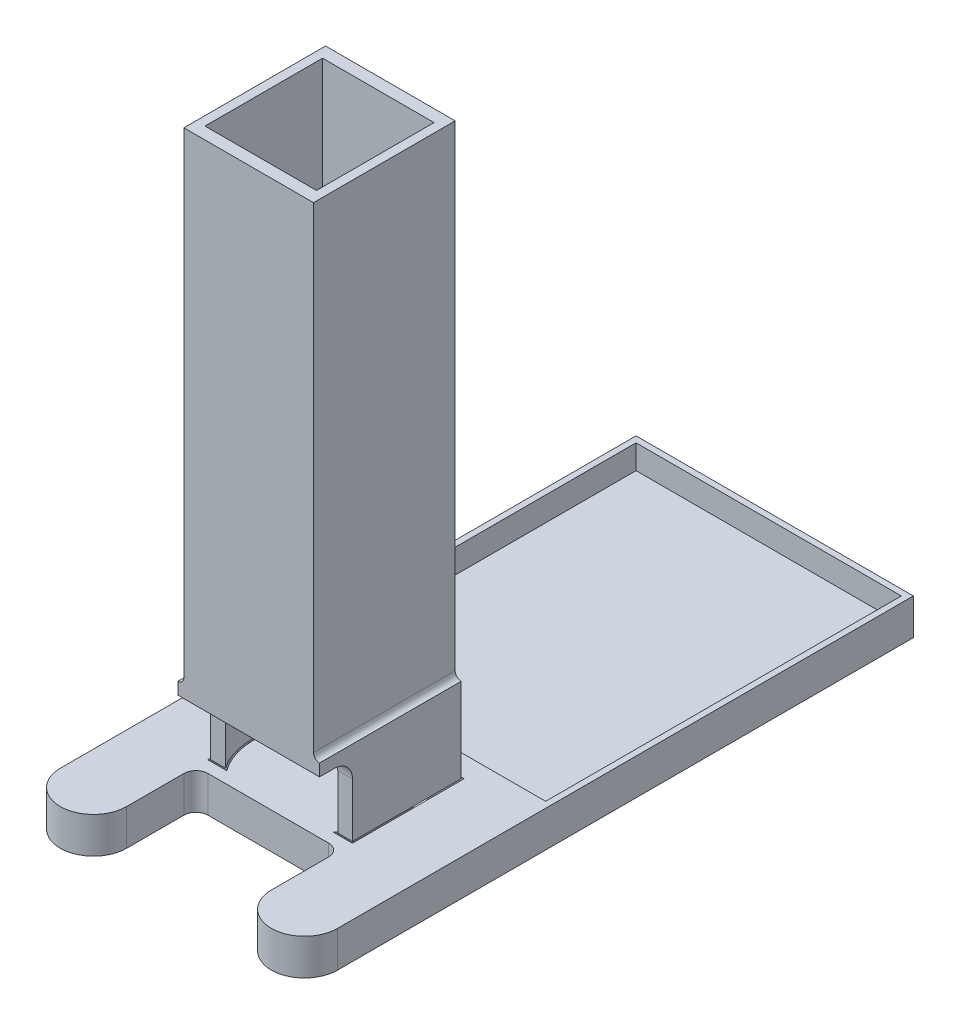
SolidWorks part; units mm, degrees
ref_plane "Front Plane" through (0, 0, 0) normal (0, 0, 1) x (1, 0, 0)
ref_plane "Top Plane" through (0, 0, 0) normal (0, 1, 0) x (1, 0, 0)
ref_plane "Right Plane" through (0, 0, 0) normal (1, 0, 0) x (0, 0, -1)
sketch "Sketch1" plane through (0, 0, 0) normal (0, 1, 0) x (1, 0, 0)
  line L0 (0, 0) -> (0, 10) construction
  line L1 (-10, -10) -> (10, -10)
  line L2 (-10, -10) -> (-10, 10)
  line L3 (-10, 10) -> (10, 10)
  line L4 (10, -10) -> (10, 10)
  line L5 (-10, -10) -> (10, 10) construction
  line L6 (-10, 10) -> (10, -10) construction
  line L7 (0, 10) -> (22.5, 10) construction
  line L8 (22.5, 10) -> (-22.5, 10)
  line L9 (-22.5, 10) -> (-22.5, 70)
  line L10 (-22.5, 70) -> (22.5, 70)
  line L11 (22.5, 70) -> (22.5, 10)
  line L12 (-22.5, 10) -> (-10, -10)
  line L13 (22.5, 10) -> (10, -10) construction
  line L14 (10, -10) -> (22.5, 10)
  line L15 (-10, -10) -> (10, -10)
  line L16 (-10, -10) -> (-10, -20)
  line L17 (-10, -20) -> (10, -20)
  line L18 (10, -10) -> (10, -20)
  circle A0 centre (0, 0) radius 4
extrude "Boss-Extrude2" add sketch "Sketch1" along normal blind 2 contours L11 L10 L9 L8 L3 | L8 L12 L2 | L4 L14 L8 | L1 L4 L3 L2 A0 | A0 | L18 L1 L16 L17 region at (-9.7172, 0, 0) region at (-14.1667, 0, -3.3333) region at (0, 0, 15) region at (14.1667, 0, -3.3333) region at (0, 0, -40) region at (0, 0, 0)
sketch "Sketch2" plane through (0, 2, 0) normal (0, 1, 0) x (1, 0, 0)
  line L0 (-21.5, 69) -> (-21.5, 11)
  line L1 (-22.5, 70) -> (22.5, 70)
  line L2 (-22.5, 70) -> (-22.5, 10)
  line L3 (-22.5, 10) -> (22.5, 10)
  line L4 (22.5, 70) -> (22.5, 10)
  line L5 (-21.5, 11) -> (21.5, 11)
  line L6 (21.5, 69) -> (21.5, 11)
  line L7 (-21.5, 69) -> (21.5, 69)
  dimension "D1" = 1
extrude "Boss-Extrude3" add sketch "Sketch2" along normal blind 4
sketch "Sketch6" plane through (0, 2, 0) normal (0, 1, 0) x (1, 0, 0)
  line L0 (-10, -20) -> (-24.7467, -20) construction
  line L1 (-22.5, 10) -> (-22.5, -20) construction
  line L2 (22.5, 10) -> (22.5, -20) construction
  line L3 (22.5, -20) -> (10, -20) construction
  line L5 (-22.5, 10) -> (22.5, 10)
  line L6 (-22.5, 10) -> (-22.5, -20)
  line L7 (-22.5, -20) -> (22.5, -20)
  line L8 (22.5, 10) -> (22.5, -20)
extrude "Boss-Extrude4" add sketch "Sketch6" against normal up to surface (2 mm away) up to face at (0, 0, -12.5)
sketch "Sketch7" plane through (0, 2, 0) normal (0, 1, 0) x (1, 0, 0)
  line L1 (0, 0) -> (0, -2) construction
  line L3 (-9.5, 9.5) -> (9.5, 9.5)
  line L4 (-9.5, 9.5) -> (-9.5, -9.5)
  line L5 (-9.5, -9.5) -> (9.5, -9.5)
  line L6 (9.5, 9.5) -> (9.5, -9.5)
  line L7 (-9.5, 9.5) -> (9.5, -9.5) construction
  line L8 (-9.5, -9.5) -> (9.5, 9.5) construction
  circle A0 centre (0, -1) radius 10
extrude "Cut-Extrude4" cut sketch "Sketch7" against normal blind 4 contours A0 L6 L3 L4 | A0 L4 L5 | A0 L5 L6 region at (0, 2, -9.2962) region at (-8.2551, 2, 7.9478) region at (8.2551, 2, 7.9478)
sketch "Sketch8" plane through (0, 2, 0) normal (0, 1, 0) x (1, 0, 0)
  line L53 (9.5, 2.1225) -> (9.5, 9.5)
  line L54 (9.5, 9.5) -> (-9.5, 9.5)
  line L55 (-9.5, 9.5) -> (-9.5, 2.1225)
  line L56 (9.5, 2.1225) -> (9.5, 9.5)
  line L57 (9.5, 9.5) -> (-9.5, 9.5)
  line L58 (-9.5, 9.5) -> (-9.5, 2.1225)
  line L60 (-9.5, -9.5) -> (-5.2678, -9.5)
  line L61 (-9.5, -4.1225) -> (-9.5, -9.5)
  line L62 (-9.5, -9.5) -> (-5.2678, -9.5)
  line L63 (-9.5, -4.1225) -> (-9.5, -9.5)
  line L66 (9.5, -9.5) -> (9.5, -4.1225)
  line L67 (5.2678, -9.5) -> (9.5, -9.5)
  line L68 (9.5, -9.5) -> (9.5, -4.1225)
  line L69 (5.2678, -9.5) -> (9.5, -9.5)
  arc A20 (9.5, 2.1225) -> (-9.5, 2.1225) centre (0, -1) ccw
  arc A21 (9.5, 2.1225) -> (-9.5, 2.1225) centre (0, -1) ccw
  arc A23 (-9.5, -4.1225) -> (-5.2678, -9.5) centre (0, -1) ccw
  arc A24 (-9.5, -4.1225) -> (-5.2678, -9.5) centre (0, -1) ccw
  arc A26 (5.2678, -9.5) -> (9.5, -4.1225) centre (0, -1) ccw
  arc A27 (5.2678, -9.5) -> (9.5, -4.1225) centre (0, -1) ccw
  dimension "D1" = 0
  dimension "D2" = 0
  dimension "D3" = 0
extrude "Boss-Extrude5" add sketch "Sketch8" along normal blind 7 separate body
sketch "Sketch11" plane through (0, 9, 0) normal (0, 1, 0) x (1, 0, 0)
  line L1 (-9.5, 9.5) -> (9.5, 9.5)
  line L2 (-9.5, 9.5) -> (-9.5, -9.5)
  line L3 (-9.5, -9.5) -> (9.5, -9.5)
  line L4 (9.5, 9.5) -> (9.5, -9.5)
extrude "Boss-Extrude6" add sketch "Sketch11" along normal blind 2
sketch "Sketch14" plane through (0, 0, 0) normal (0, -1, 0) x (1, 0, 0)
  line L0 (0, 0) -> (0, 1) construction
  circle A1 centre (0, 1) radius 4
extrude "Cut-Extrude7" cut sketch "Sketch14" against normal blind 19
sketch "Sketch15" plane through (0, 11, 0) normal (0, 1, 0) x (1, 0, 0)
  line L0 (9.5, 8.5) -> (-8.5, 8.5)
  line L1 (-8.5, 8.5) -> (-8.5, -8.5)
  line L2 (-8.5, -8.5) -> (9.5, -8.5)
  line L3 (8.5, -9.5) -> (8.5, 9.5)
  line L4 (0, 0) -> (9.5, 0) construction
  line L5 (9.5, 0) -> (-9.5, 0) construction
  line L6 (0, 0) -> (0, -8) construction
  line L7 (9.5, -9.5) -> (9.5, 9.5)
  line L8 (-9.5, 9.5) -> (-9.5, -9.5)
  line L9 (-9.5, -9.5) -> (9.5, -9.5)
  line L10 (9.5, -9.5) -> (9.5, 9.5)
  line L11 (9.5, 9.5) -> (-9.5, 9.5)
  line L12 (-9.5, 9.5) -> (-9.5, -9.5)
  line L13 (-9.5, -9.5) -> (9.5, -9.5)
  line L14 (9.5, -9.5) -> (9.5, 9.5)
  line L15 (9.5, 9.5) -> (-9.5, 9.5)
  line L16 (0, -8) -> (6.9282, -4)
  line L17 (6.9282, -4) -> (6.9282, 4)
  line L18 (6.9282, 4) -> (0, 8)
  line L19 (0, 8) -> (-6.9282, 4)
  line L20 (-6.9282, 4) -> (-6.9282, -4)
  line L21 (-6.9282, -4) -> (0, -8)
  line L22 (9.5, 9.5) -> (-9.5, 9.5)
  line L23 (-9.5, 9.5) -> (-9.5, -9.5)
  circle A0 centre (0, 0) radius 6.9282 construction
  line M17 (-9.5, 9.5) -> (-9.5, -9.5)
  line M18 (-9.5, -9.5) -> (9.5, -9.5)
  line M19 (9.5, -9.5) -> (9.5, 9.5)
  line M20 (9.5, 9.5) -> (-9.5, 9.5)
  dimension "D2" = 0
  dimension "D1" = 0
  dimension "D3" = 1
extrude "Boss-Extrude7" add sketch "Sketch15" along normal blind 80 contours L3 L2 L1 L0 M18 M20 M17 | L3 L2 L0 M19 | L3 L0 M19 M20 | L3 L2 M18 M19 region at (9, 11, 0) region at (9, 11, -9) region at (0, 11, -8.7617) region at (9, 11, 9)
sketch "Sketch18" plane through (0, 0, 9.5) normal (0, 0, 1) x (1, 0, 0)
  line L1 (-9.5, 91) -> (9.5, 91)
  line L2 (-9.5, 91) -> (-9.5, 11)
  line L3 (-9.5, 11) -> (9.5, 11)
  line L4 (9.5, 91) -> (9.5, 11)
extrude "Boss-Extrude8" add sketch "Sketch18" along normal blind 2
fillet "Fillet2" radius 1.9 1 edges at (0, 11, 9.5) type face fillet first side face at (0, 6, 9.5) second side face at (0, 11, 10.5)
sketch "Sketch20" plane through (-22.5, 0, 0) normal (-1, 0, 0) x (0, 0, 1)
  line L12 (-70, 0) -> (20, 0)
  line L13 (20, 0) -> (20, 2)
  line L14 (20, 2) -> (-10, 2)
  line L15 (-10, 2) -> (-10, 6)
  line L16 (-10, 2) -> (-10, 6)
  line L17 (-70, 6) -> (-70, 0)
  line L18 (-70, 0) -> (20, 0)
  line L19 (20, 0) -> (20, 2)
  line L20 (20, 2) -> (-10, 2)
  line L23 (-70, 6) -> (-70, 0)
  line L24 (-10, 6) -> (-70, 6)
  line L25 (-10, 6) -> (-70, 6)
  dimension "D1" = 0
extrude "Boss-Extrude9" add sketch "Sketch20" along normal blind 0.5
sketch "Sketch21" plane through (22.5, 0, 0) normal (1, 0, 0) x (0, 0, -1)
  line L12 (-20, 0) -> (70, 0)
  line L13 (70, 0) -> (70, 6)
  line L14 (70, 6) -> (10, 6)
  line L15 (70, 6) -> (10, 6)
  line L16 (10, 2) -> (-20, 2)
  line L17 (-20, 2) -> (-20, 0)
  line L18 (-20, 0) -> (70, 0)
  line L19 (70, 0) -> (70, 6)
  line L22 (10, 2) -> (-20, 2)
  line L23 (-20, 2) -> (-20, 0)
  line L24 (10, 6) -> (10, 2)
  line L25 (10, 6) -> (10, 2)
  dimension "D1" = 0
extrude "Boss-Extrude10" add sketch "Sketch21" along normal blind 0.5
sketch "Sketch22" plane through (0, 0, -70) normal (0, 0, -1) x (-1, 0, 0)
  line L8 (-23, 0) -> (23, 0)
  line L9 (23, 0) -> (23, 6)
  line L10 (23, 6) -> (-23, 6)
  line L11 (-23, 6) -> (-23, 0)
  line L12 (-23, 0) -> (23, 0)
  line L13 (23, 0) -> (23, 6)
  line L15 (-23, 6) -> (-23, 0)
  line L17 (23, 6) -> (-23, 6)
  dimension "D1" = 0
extrude "Boss-Extrude11" add sketch "Sketch22" along normal blind 1
sketch "Sketch23" plane through (0, 6, 0) normal (0, 1, 0) x (1, 0, 0)
  line L0 (21.5, 69) -> (22, 69) construction
  line L1 (22, 69) -> (22, 70) construction
  line L2 (-21.5, 11) -> (-22, 11) construction
  line L4 (-22, 11) -> (22, 11)
  line L5 (-22, 11) -> (-22, 70)
  line L6 (-22, 70) -> (22, 70)
  line L7 (22, 11) -> (22, 70)
extrude "Cut-Extrude10" cut sketch "Sketch23" against normal up to surface (4 mm away) up to face at (0, 2, -40)
sketch "Sketch24" plane through (0, 0, 0) normal (0, -1, 0) x (1, 0, 0)
  line L1 (-9.5, -9.5) -> (9.5, -9.5)
  line L2 (-9.5, -9.5) -> (-9.5, 9.5)
  line L3 (-9.5, 9.5) -> (9.5, 9.5)
  line L4 (9.5, -9.5) -> (9.5, 9.5)
extrude "Boss-Extrude12" add sketch "Sketch24" against normal up to surface (2 mm away) up to face at (0, 2, 5)
sketch "Sketch25" plane through (0, 91, 0) normal (0, 1, 0) x (1, 0, 0)
  line L1 (-9.5, -11.5) -> (9.5, -11.5)
  line L2 (-9.5, -11.5) -> (-9.5, 9.5)
  line L3 (-9.5, 9.5) -> (9.5, 9.5)
  line L4 (9.5, -11.5) -> (9.5, 9.5)
extrude "Cut-Extrude11" cut sketch "Sketch25" against normal up to surface (89 mm away) up to face at (-8.2474, 2, 7.8319)
sketch "Sketch28" plane through (0, 0, -10) normal (0, 0, 1) x (1, 0, 0)
  line L1 (-23, 6) -> (23, 6)
  line L2 (-23, 6) -> (-23, 2)
  line L3 (-23, 2) -> (23, 2)
  line L4 (23, 6) -> (23, 2)
extrude "Boss-Extrude13" add sketch "Sketch28" along normal up to surface (30 mm away) up to face at (0, 1, 20)
sketch "Sketch29" plane through (0, 6, 0) normal (0, 1, 0) x (1, 0, 0)
  line L0 (22, 11) -> (22, -20) construction
  line L1 (-23, -20) -> (23, -20) construction
  line L2 (-22, 11) -> (-22, -20) construction
  line L3 (-22, 11) -> (22, -20) construction
sketch "Sketch30" plane through (0, 6, 0) normal (0, 1, 0) x (1, 0, 0)
  line L0 (-22, 11) -> (22, -20) construction
  line L1 (-12, 7.5) -> (12, 7.5)
  line L2 (-11, 6.5) -> (11, 6.5)
  line L3 (-11, 6.5) -> (-11, -15.5)
  line L4 (-11, -15.5) -> (11, -15.5)
  line L5 (11, 6.5) -> (11, -15.5)
  line L6 (-11, 6.5) -> (11, -15.5) construction
  line L7 (-11, -15.5) -> (11, 6.5) construction
  line L8 (12, 7.5) -> (12, -16.5)
  line L9 (-12, -16.5) -> (12, -16.5)
  line L10 (-12, 7.5) -> (-12, -16.5)
  line L12 (-12, 7.5) -> (-8.3083, 7.5)
  line L13 (-12, 7.5) -> (-12, 3.8083)
  line L16 (12, 7.5) -> (8.149, 7.5)
  line L17 (12, 7.5) -> (12, 3.649)
  line L20 (-12, -16.5) -> (-6.5453, -16.5)
  line L21 (-12, -16.5) -> (-12, -11.0453)
  line L28 (12, -16.5) -> (-12, -16.5)
  line L29 (12, -16.5) -> (12, -11.0453)
  line L30 (12, -11.0453) -> (-12, -11.0453)
  line L31 (-12, -16.5) -> (-12, -11.0453)
  circle A0 centre (0, -4.5) radius 4
  circle A1 centre (0, -4.5) radius 10
  circle A2 centre (0, -4.5) radius 11
  dimension "D1" = 1
  dimension "D2" = 1
extrude "Cut-Extrude20" cut sketch "Sketch30" against normal blind 12 contours L30 L8 L1 L10 L3 L2 L5 | A2 L2 L3 | A2 L3 L30 | A2 L5 L2 | A2 L30 L5 region at (-10.1541, 6, -7.1967) region at (-10.3648, 6, 9.4428) region at (-8.543, 6, -4.043) region at (8.543, 6, -4.043) region at (10.3648, 6, 9.4428)
sketch "Sketch35" plane through (0, 6, 0) normal (0, 1, 0) x (1, 0, 0)
  line L8 (22.75, -19.75) -> (22.75, 70.75)
  line L9 (22.75, 70.75) -> (-22.75, 70.75)
  line L10 (-22.75, 70.75) -> (-22.75, -19.75)
  line L11 (-22.75, -19.75) -> (22.75, -19.75)
  line L12 (22.75, -19.75) -> (22.75, 70.75)
  line L13 (22.75, 70.75) -> (-22.75, 70.75)
  line L14 (-22.75, 70.75) -> (-22.75, -19.75)
  line L15 (-22.75, -19.75) -> (22.75, -19.75)
  line L34 (-11.75, 7.25) -> (-11.75, -10.7953)
  line L35 (11.75, -10.7953) -> (11.75, 7.25)
  line L36 (9.3237, -10.7953) -> (11.75, -10.7953)
  line L37 (-11.75, -10.7953) -> (-9.3237, -10.7953)
  line L38 (11.75, 7.25) -> (-11.75, 7.25)
  line L39 (-11.75, 7.25) -> (-11.75, -10.7953)
  line L40 (11.75, -10.7953) -> (11.75, 7.25)
  line L41 (9.3237, -10.7953) -> (11.75, -10.7953)
  line L42 (-11.75, -10.7953) -> (-9.3237, -10.7953)
  line L43 (11.75, 7.25) -> (-11.75, 7.25)
  arc A5 (9.3237, -10.7953) -> (-9.3237, -10.7953) centre (0, -4.5) ccw
  arc A6 (9.3237, -10.7953) -> (-9.3237, -10.7953) centre (0, -4.5) ccw
  dimension "D1" = 0.25
  dimension "D2" = 0.25
extrude "Boss-Extrude16" add sketch "Sketch35" along normal blind 12 separate body contours L39 L42 A6 L41 L40 L43
sketch "Sketch37" plane through (0, 18, 0) normal (0, 1, 0) x (1, 0, 0)
  line L1 (11.75, 7.25) -> (-11.75, 7.25)
  line L2 (11.75, 7.25) -> (11.75, -16.25)
  line L3 (11.75, -16.25) -> (-11.75, -16.25)
  line L4 (-11.75, 7.25) -> (-11.75, -16.25)
extrude "Boss-Extrude17" add sketch "Sketch37" along normal blind 2
fillet "Fillet3" radius 3 1 edges at (10.5369, 18, 10.7953) type face fillet first side face at (10.5369, 12, 10.7953) second side face at (0, 18, 9.6893)
fillet "Fillet7" radius 2 1 edges at (-10.5369, 18, 10.7953) type face fillet first side face at (-10.5369, 12, 10.7953) second side face at (0.1039, 18, 10.4728)
sketch "Sketch38" plane through (0, 20, 0) normal (0, 1, 0) x (1, 0, 0)
  line L0 (-11.75, 7.25) -> (11.75, -16.25) construction
  line L1 (-10.75, -16.25) -> (-10.75, 7.25)
  line L2 (-8.75, -14.25) -> (8.75, -14.25)
  line L3 (-8.75, -14.25) -> (-8.75, 5.25)
  line L4 (-8.75, 5.25) -> (8.75, 5.25)
  line L5 (8.75, -14.25) -> (8.75, 5.25)
  line L6 (-8.75, -14.25) -> (8.75, 5.25) construction
  line L7 (-8.75, 5.25) -> (8.75, -14.25) construction
  line L8 (-10.75, 7.25) -> (10.75, 7.25)
  line L9 (10.75, -16.25) -> (10.75, 7.25)
  line L10 (-10.75, -16.25) -> (10.75, -16.25)
  point P4 (0, -4.5)
  dimension "D1" = 2
extrude "Boss-Extrude18" add sketch "Sketch38" along normal blind 80
sketch "Sketch39" plane through (0, 20, 0) normal (0, 1, 0) x (1, 0, 0)
  line L0 (-8.75, -14.25) -> (8.75, 5.25) construction
  circle A0 centre (0, -4.5) radius 4
extrude "Cut-Extrude21" cut sketch "Sketch39" against normal up to surface (14 mm away) up to face at (0, 6, -40.5)
fillet "Fillet8" radius 1 1 edges at (10.75, 20, 4.5) type face fillet first side face at (10.75, 60, 4.5) second side face at (11.25, 20, 4.5)
fillet "Fillet9" radius 1 1 edges at (-10.75, 20, 4.5) type face fillet first side face at (-10.75, 60, 4.5) second side face at (-11.25, 20, 4.5)
sketch "Sketch40" plane through (0, 0, 20) normal (0, 0, 1) x (1, 0, 0)
  line L8 (-23, 0) -> (23, 0)
  line L9 (23, 0) -> (23, 6)
  line L10 (23, 6) -> (-23, 6)
  line L11 (-23, 6) -> (-23, 0)
  line L12 (-23, 0) -> (23, 0)
  line L13 (23, 0) -> (23, 6)
  line L14 (23, 6) -> (-23, 6)
  line L15 (-23, 6) -> (-23, 0)
  dimension "D1" = 0
extrude "Boss-Extrude19" add sketch "Sketch40" along normal blind 5
sketch "Sketch41" plane through (0, 0, 25) normal (0, 0, 1) x (1, 0, 0)
  line L8 (-23, 6) -> (-23, 0)
  line L9 (-23, 0) -> (23, 0)
  line L10 (23, 0) -> (23, 6)
  line L11 (23, 6) -> (-23, 6)
  line L12 (-23, 6) -> (-23, 0)
  line L13 (-23, 0) -> (23, 0)
  line L14 (23, 0) -> (23, 6)
  line L15 (23, 6) -> (-23, 6)
  dimension "D1" = 0
extrude "Boss-Extrude20" add sketch "Sketch41" along normal blind 5
sketch "Sketch42" plane through (0, 6, 0) normal (0, 1, 0) x (1, 0, 0)
  line L0 (23, -30) -> (-23, -30) construction
  line L1 (-12, -30) -> (12, -30)
  line L2 (-12, -30) -> (-12, -16)
  line L3 (-12, -16) -> (12, -16)
  line L4 (12, -30) -> (12, -16)
extrude "Cut-Extrude22" cut sketch "Sketch42" against normal blind 15
sketch "Sketch43" plane through (0, 6, 0) normal (0, 1, 0) x (1, 0, 0)
  line L1 (-12, -16) -> (12, -16)
  line L2 (-12, -16) -> (-12, -13)
  line L3 (-12, -13) -> (12, -13)
  line L4 (12, -16) -> (12, -13)
extrude "Cut-Extrude23" cut sketch "Sketch43" against normal blind 15
fillet "Fillet12" 2 edges at (-23, 3, 30) (-12, 3, 30) type full round first side face at (-23, 3, -20.5) second side face at (-12, 3, 21.5) middle face at (-17.5, 3, 30)
fillet "Fillet13" 2 edges at (12, 3, 30) (23, 3, 30) type full round first side face at (12, 3, 21.5) second side face at (23, 3, -20.5) middle face at (17.5, 3, 30)
fillet "Fillet14" radius 2 1 edges at (-12, 3, 13) type face fillet first side face at (0, 3, 13) second side face at (-12, 3, 18.75)
fillet "Fillet15" radius 2 1 edges at (12, 3, 13) type face fillet first side face at (12, 3, 18.75) second side face at (1, 3, 13)
sketch "Sketch44" plane through (0, 100, 0) normal (0, 1, 0) x (1, 0, 0)
  line L0 (-8.75, 5.25) -> (-9.25, 5.25) construction
  line L1 (8.75, -14.25) -> (9.25, -14.25) construction
  line L3 (9.25, -14.25) -> (-9.25, -14.25)
  line L4 (9.25, -14.25) -> (9.25, 5.25)
  line L5 (9.25, 5.25) -> (-9.25, 5.25)
  line L6 (-9.25, -14.25) -> (-9.25, 5.25)
extrude "Cut-Extrude24" cut sketch "Sketch44" against normal up to surface (80 mm away) up to face at (0, 20, 8.5)
